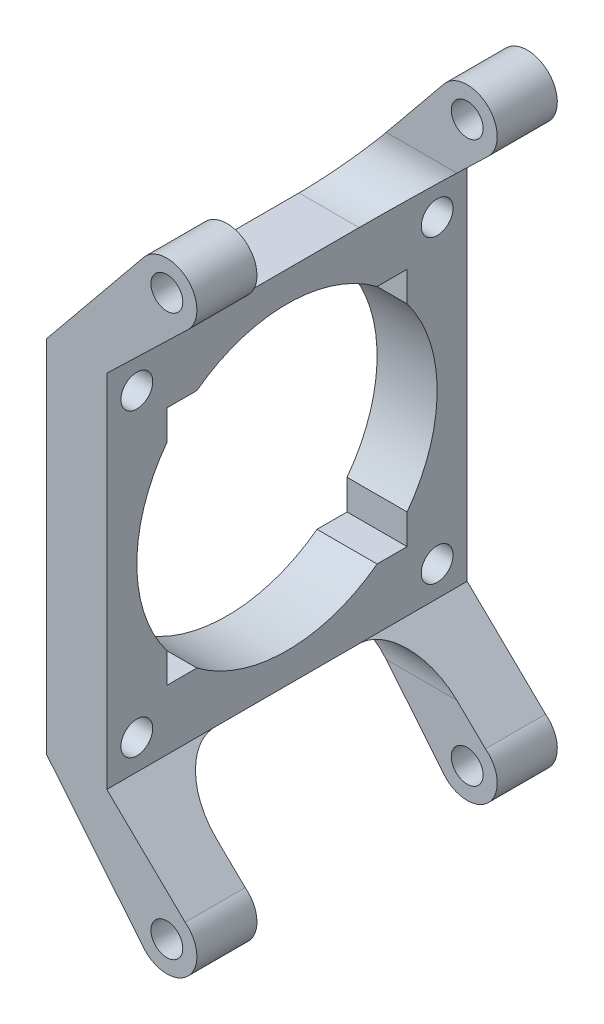
SolidWorks part; units mm, degrees
ref_plane "前视基准面" through (0, 0, 0) normal (0, 0, 1) x (1, 0, 0)
ref_plane "上视基准面" through (0, 0, 0) normal (0, 1, 0) x (1, 0, 0)
ref_plane "右视基准面" through (0, 0, 0) normal (1, 0, 0) x (0, 0, -1)
sketch "草图1" plane through (0, 0, 0) normal (0, 0, 1) x (1, 0, 0)
  line L0 (-20, -76.6) -> (-3.8738, -96.3612)
  line L1 (-20, -16.6) -> (-10, -16.6)
  line L2 (-20, -16.6) -> (-20, -76.6)
  line L3 (-20, -76.6) -> (-10, -76.6)
  line L4 (-10, -16.6) -> (-10, -76.6)
  line L5 (-10, -76.6) -> (3.0446, -89.2339)
  line L6 (-10, -16.6) -> (3.4722, -3.5977)
  line L7 (-20, -16.6) -> (-3.8738, 3.1612)
  line L8 (-20, -26.6) -> (-10, -26.6)
  line L9 (-20, -66.6) -> (-10, -66.6)
  circle A0 centre (0, 0) radius 2.65
  circle A1 centre (0, 0) radius 5
  circle A4 centre (0, -93.2) radius 2.65
  circle A5 centre (0, -93.2) radius 5
  point P11 (-15, -76.6)
  dimension "D1" = 5.3
  dimension "D2" = 10
  dimension "D3" = 60
  dimension "D4" = 10
  dimension "D5" = 5.3
  dimension "D6" = 10
  dimension "D7" = 16.6
  dimension "D8" = 10
  dimension "D9" = 10
  dimension "D10" = 93.2
  dimension "D11" = 10
extrude "凸台-拉伸1" add sketch "草图1" along normal blind 10 contours L2 L9 L4 L8 | L2 L8 L4 L1 | A1 L7 L1 L6 | A1 A0 | L9 L2 L3 L4 | A5 L5 L3 L0 | A5 A4 region at (-8.8918, -83.8381, 0) region at (-15, -71.6, 0) region at (-3.4862, -89.8159, 0) region at (-15, -46.6, 0) region at (-15, -21.6, 0) region at (-8.8773, -9.3595, 0) region at (1.6305, 4.5768, 0)
extrude "凸台-拉伸2" add sketch "草图1<5>" along normal blind 50 contours L2 L8 L4 L1 | L9 L2 L3 L4 region at (-15, -71.6, 0) region at (-15, -21.6, 0)
sketch "草图1<5>" plane through (0, 0, 0) normal (0, 0, 1) x (1, 0, 0) same geometry as "草图1"
extrude "凸台-拉伸3" add sketch "草图1<6>" along normal blind 10 from surface contours A1 A0 | A1 L7 L1 L6 | L2 L8 L4 L1 | L2 L9 L4 L8 | L9 L2 L3 L4 | A5 A4 | A5 L5 L3 L0 region at (-8.8918, -83.8381, 0) region at (-15, -71.6, 0) region at (-3.4862, -89.8159, 0) region at (-15, -46.6, 0) region at (-15, -21.6, 0) region at (-8.8773, -9.3595, 0) region at (1.6305, 4.5768, 0) starting at face at (-15, -21.6, 50)
sketch "草图1<6>" plane through (0, 0, 0) normal (0, 0, 1) x (1, 0, 0) same geometry as "草图1"
sketch "草图2" plane through (-20, 0, 0) normal (-1, 0, 0) x (0, 0, 1)
  line L1 (60, -76.6) -> (60, -16.6) construction
  line L2 (50, -76.6) -> (10, -76.6) construction
  circle A0 centre (30, -46.6) radius 25
  dimension "D1" = 50
  dimension "D2" = 30
  dimension "D3" = 30
extrude "切除-拉伸1" cut sketch "草图2" against normal through all
sketch "草图3" plane through (-10, 0, 0) normal (1, 0, 0) x (0, 0, -1)
  line L0 (0, -16.6) -> (0, -76.6) construction
  line L2 (-10, -16.6) -> (0, -16.6) construction
  circle A0 centre (-55, -21.6) radius 2.65
  circle A1 centre (-5, -21.6) radius 2.65
  circle A2 centre (-55, -71.6) radius 2.65
  circle A3 centre (-5, -71.6) radius 2.65
  dimension "D1" = 5.3
  dimension "D2" = 5.3
  dimension "D4" = 5.3
  dimension "D5" = 5.3
  dimension "D3" = 50
  dimension "D6" = 50
  dimension "D7" = 50
  dimension "D8" = 50
  dimension "D9" = 5
  dimension "D10" = 5
extrude "切除-拉伸2" cut sketch "草图3" against normal through all
fillet "圆角1" radius 8 4 edges at (-15, -76.6, 50) (-15, -76.6, 10) (-15, -16.6, 10) (-15, -16.6, 50)
